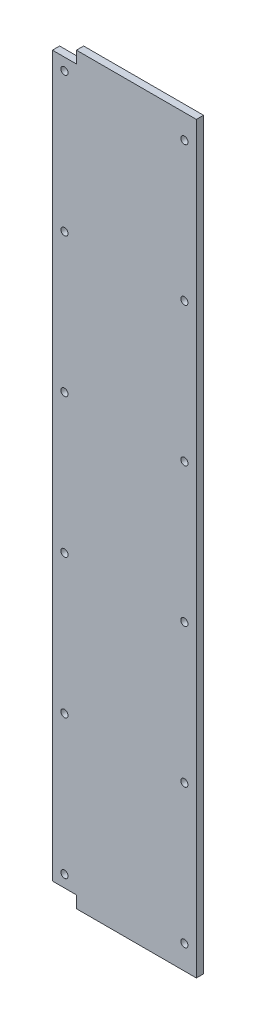
SolidWorks part; units mm, degrees
ref_plane "Plan de face" through (0, 0, 0) normal (0, 0, 1) x (1, 0, 0)
ref_plane "Plan de dessus" through (0, 0, 0) normal (0, 1, 0) x (1, 0, 0)
ref_plane "Plan de droite" through (0, 0, 0) normal (1, 0, 0) x (0, 0, -1)
sketch "Esquisse1" plane through (0, 0, 0) normal (0, 0, 1) x (1, 0, 0)
  line L0 (-30, 0) -> (30, 0) construction
  line L1 (30, -155) -> (-30, -155)
  line L2 (30, -155) -> (30, 155)
  line L3 (30, 155) -> (-30, 155)
  line L4 (-30, -155) -> (-30, 155)
  line L5 (30, -155) -> (-30, 155) construction
  line L6 (30, 155) -> (-30, -155) construction
  line L7 (-30, -155) -> (-20, -155)
  line L8 (-30, -155) -> (-30, -150)
  line L9 (-30, -150) -> (-20, -150)
  line L10 (-20, -155) -> (-20, -150)
  line L11 (-30, 150) -> (-20, 150)
  line L12 (-20, 155) -> (-20, 150)
  line L13 (-30, 155) -> (-20, 155)
  line L14 (-30, 155) -> (-30, 150)
  line L15 (-25, -150) -> (-25, 150) construction
  line L16 (0, 155) -> (0, -155) construction
  line L17 (-25, -145) -> (-25, -87) construction
  circle A0 centre (-25, -145) radius 1.5
  circle A1 centre (-25, -87) radius 1.5
  circle A2 centre (-25, -29) radius 1.5
  circle A3 centre (-25, 29) radius 1.5
  circle A4 centre (-25, 87) radius 1.5
  circle A5 centre (-25, 145) radius 1.5
  circle A6 centre (25, -87) radius 1.5
  circle A7 centre (25, -145) radius 1.5
  circle A8 centre (25, -29) radius 1.5
  circle A9 centre (25, 29) radius 1.5
  circle A10 centre (25, 87) radius 1.5
  circle A11 centre (25, 145) radius 1.5
  point P0 (0, 0)
  point P44 (-25, 160)
  point P45 (-25, 160)
  dimension "D5" = 3
  dimension "D1" = 60
  dimension "D2" = 310
  dimension "D3" = 10
  dimension "D4" = 5
  dimension "D6" = 5
  dimension "D7" = 58
  dimension "D8" = 6
extrude "Boss.-Extru.1" add sketch "Esquisse1" along normal blind 3 contours L3 L12 L11 L4 L9 L10 L1 L2 A10 A8 A6 A5 A4 A3 A2 A1 A0 A7 A9 A11 region at (0.1358, 0, 0)
